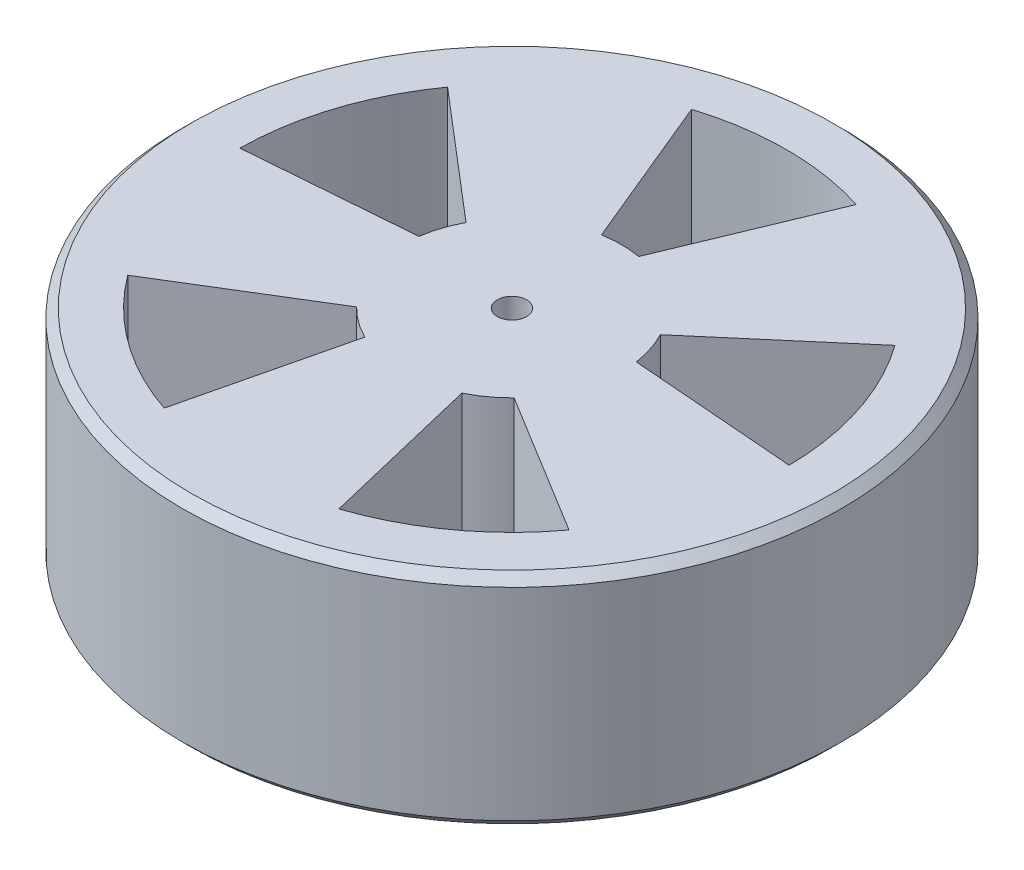
SolidWorks part; units mm, degrees
ref_plane "Front Plane" through (0, 0, 0) normal (0, 0, 1) x (1, 0, 0)
ref_plane "Top Plane" through (0, 0, 0) normal (0, 1, 0) x (1, 0, 0)
ref_plane "Right Plane" through (0, 0, 0) normal (1, 0, 0) x (0, 0, -1)
sketch "Sketch1" plane through (0, 0, 0) normal (0, 1, 0) x (1, 0, 0)
  circle A0 centre (0, 0) radius 76.2
  dimension "D1" = 152.4
extrude "Boss-Extrude1" add sketch "Sketch1" along normal blind 50.8
chamfer "Chamfer1" distance 2.032 angle 45 2 edges at (0, 0, 76.2) (0, 50.8, 76.2)
sketch "Sketch2" plane through (0, 50.8, 0) normal (0, 1, 0) x (1, 0, 0)
  line L0 (-12.7, 0) -> (0, 0) construction
  line L1 (0, 0) -> (12.7, 0) construction
  circle A0 centre (0, 0) radius 25.4 construction
  circle A1 centre (-12.7, 0) radius 3.175
  circle A2 centre (12.7, 0) radius 3.175
  dimension "D1" = 6.35
  dimension "D2" = 50.8
  dimension "D3" = 12.7
  dimension "D4" = 12.7
extrude "Cut-Extrude1" [suppressed] cut sketch "Sketch2" against normal through all both and the other way through all
sketch "Sketch3" plane through (0, 50.8, 0) normal (0, 1, 0) x (1, 0, 0)
  line L0 (0, 25.4) -> (0, 63.5) construction
  line L1 (-4.3262, 25.0289) -> (-19.05, 60.5751)
  line L2 (4.3262, 25.0289) -> (19.05, 60.5751)
  line L3 (22.467, 11.8488) -> (51.7236, 36.8364)
  line L4 (25.1407, 3.6198) -> (63.4972, 0.6011)
  line L5 (18.2116, -17.7059) -> (51.0169, -37.809)
  line L6 (11.2116, -22.7917) -> (20.1934, -60.2036)
  line L7 (-11.2116, -22.7917) -> (-20.1934, -60.2036)
  line L8 (-18.2116, -17.7059) -> (-51.0169, -37.809)
  line L9 (-25.1407, 3.6198) -> (-63.4972, 0.6011)
  line L10 (-22.467, 11.8488) -> (-51.7236, 36.8364)
  arc A0 (4.3262, 25.0289) -> (-4.3262, 25.0289) centre (0, 0) ccw
  arc A1 (19.05, 60.5751) -> (-19.05, 60.5751) centre (0, 0) ccw
  circle A2 centre (0, 0) radius 76.2 construction
  arc A3 (-4.3262, 25.0289) -> (4.3262, 25.0289) centre (0, 0) ccw construction
  arc A4 (-19.05, 60.5751) -> (19.05, 60.5751) centre (0, 0) ccw construction
  arc A5 (25.1407, 3.6198) -> (22.467, 11.8488) centre (0, 0) ccw
  arc A6 (63.4972, 0.6011) -> (51.7236, 36.8364) centre (0, 0) ccw
  arc A7 (11.2116, -22.7917) -> (18.2116, -17.7059) centre (0, 0) ccw
  arc A8 (20.1934, -60.2036) -> (51.0169, -37.809) centre (0, 0) ccw
  arc A9 (-18.2116, -17.7059) -> (-11.2116, -22.7917) centre (0, 0) ccw
  arc A10 (-51.0169, -37.809) -> (-20.1934, -60.2036) centre (0, 0) ccw
  arc A11 (-22.467, 11.8488) -> (-25.1407, 3.6198) centre (0, 0) ccw
  arc A12 (-51.7236, 36.8364) -> (-63.4972, 0.6011) centre (0, 0) ccw
  point P28 (0, 0)
  dimension "D1" = 12.7
  dimension "D2" = 50.8
  dimension "D3" = 45
  dimension "D4" = 22.5
  dimension "D5" = 19.05
  dimension "D6" = 19.05
  dimension "D7" = 5
extrude "Cut-Extrude2" cut sketch "Sketch3" against normal through all both and the other way through all
sketch "Sketch4" plane through (0, 50.8, 0) normal (0, 1, 0) x (1, 0, 0)
  point P0 (0, 0)
hole_wizard "1/4 Clearance Hole1" positions "Sketch4" profile "Sketch5" hole size "1/4" standard "ANSI Inch" end condition through all
sketch "Sketch5" plane through (0, 50.8, 0) normal (1, 0, 0) x (0, 0, 1)
  line L0 (0, 0) -> (0, 50.8)
  line L1 (0, 50.8) -> (3.3782, 50.8)
  line L2 (3.3782, 50.8) -> (3.3782, 0)
  line L5 (3.3782, 0) -> (0, 0)
  line L11 (0, -6.35) -> (0, 107.95) construction
  dimension "Thru Hole Dia." = 6.7564
  dimension "Thru Hole Depth" = 50.8
equation "\"OD\"= 6"
equation "\"offset\"= 0"
equation "\"L\"= 2"
equation "\"D1@Sketch1\"=\"OD\"-\"offset\""
equation "\"D1@Boss-Extrude1\"=\"L\""
